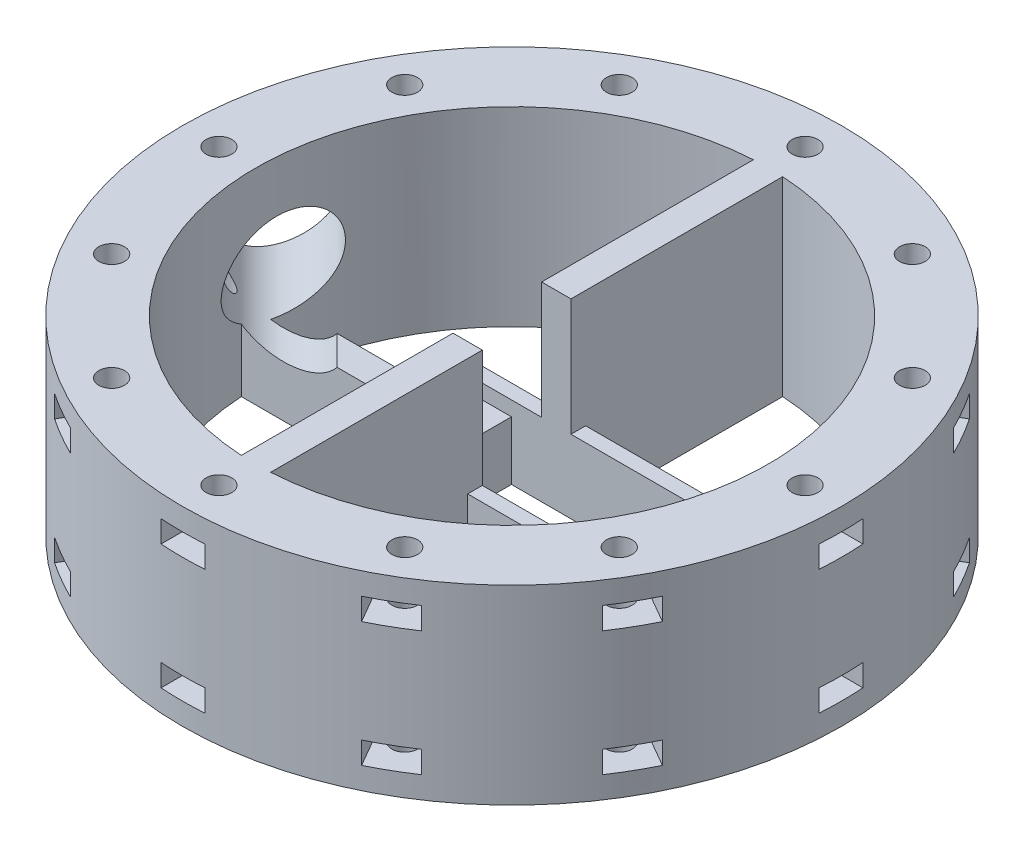
SolidWorks part; units mm, degrees
ref_plane "Front Plane" through (0, 0, 0) normal (0, 0, 1) x (1, 0, 0)
ref_plane "Top Plane" through (0, 0, 0) normal (0, 1, 0) x (1, 0, 0)
ref_plane "Right Plane" through (0, 0, 0) normal (1, 0, 0) x (0, 0, -1)
sketch "Sketch2" plane through (0, 0, 0) normal (0, 1, 0) x (1, 0, 0)
  line L0 (0, 0) -> (0, 45) construction
  circle A0 centre (0, 0) radius 45
  dimension "D1" = 90
extrude "Boss-Extrude1" add sketch "Sketch2" along normal blind 10
sketch "Sketch3" plane through (0, 10, 0) normal (0, 1, 0) x (1, 0, 0)
  line L0 (0, 45) -> (0, 0) construction
  line L1 (0, 0) -> (45, 0) construction
  line L2 (-10.95, 6.05) -> (21.3, 6.05)
  line L3 (21.3, 6.05) -> (21.3, -6.05)
  line L4 (-10.95, 6.05) -> (-10.95, -6.05)
  line L5 (-10.95, -6.05) -> (21.3, -6.05)
  circle A0 centre (0, 0) radius 45 construction
  point P12 (21.3, 0)
  point P13 (-10.95, 0)
  dimension "D1" = 32.25
  dimension "D2" = 10.95
  dimension "D3" = 12.1
extrude "Cut-Extrude1" cut sketch "Sketch3" against normal blind 2
sketch "Sketch4" plane through (0, 8, 0) normal (0, 1, 0) x (1, 0, 0)
  line L0 (5.175, 6.05) -> (5.175, -6.05) construction
  line L1 (21.3, 6.05) -> (-10.95, 6.05) construction
  line L2 (-10.95, -6.05) -> (21.3, -6.05) construction
  line L4 (-6.125, 6.05) -> (16.475, 6.05)
  line L5 (-6.125, 6.05) -> (-6.125, -6.05)
  line L6 (-6.125, -6.05) -> (16.475, -6.05)
  line L7 (16.475, 6.05) -> (16.475, -6.05)
  line L8 (-6.125, 6.05) -> (16.475, -6.05) construction
  line L9 (-6.125, -6.05) -> (16.475, 6.05) construction
  point P6 (5.175, 0)
  dimension "D1" = 22.6
extrude "Cut-Extrude2" cut sketch "Sketch4" against normal through all
sketch "Sketch6" plane through (0, 8, 0) normal (0, 1, 0) x (1, 0, 0)
  line L0 (-10.95, 0) -> (21.3, 0) construction
  line L1 (-10.95, 6.05) -> (-10.95, -6.05) construction
  line L2 (21.3, -6.05) -> (21.3, 6.05) construction
  line L3 (5.175, 6.05) -> (5.175, -6.05) construction
  line L4 (21.3, 6.05) -> (-10.95, 6.05) construction
  line L5 (-10.95, -6.05) -> (21.3, -6.05) construction
  circle A0 centre (-8.675, 0) radius 1
  circle A1 centre (19.025, 0) radius 1
  dimension "D1" = 2
  dimension "D2" = 27.7
extrude "Cut-Extrude4" cut sketch "Sketch6" against normal through all
sketch "Sketch9" plane through (0, 10, 0) normal (0, 1, 0) x (1, 0, 0)
  line L0 (-10.95, 6.05) -> (-10.95, -6.05) construction
  line L1 (-12.95, 8.05) -> (-2, 8.05)
  line L2 (-12.95, 8.05) -> (-12.95, 2)
  line L3 (-12.95, -8.05) -> (-2, -8.05)
  line L4 (-12.95, 2) -> (-34.9428, 2)
  line L6 (21.3, 6.05) -> (-10.95, 6.05) construction
  line L7 (0, 0) -> (-31.825, 0) construction
  line L8 (0, 0) -> (0, 31.7606) construction
  line L9 (-2, 34.9428) -> (-2, 8.05)
  line L10 (2, 34.9428) -> (2, 8.05)
  line L11 (-12.95, -2) -> (-34.9428, -2)
  line L12 (2, -34.9428) -> (2, -8.05)
  line L13 (-2, -34.9428) -> (-2, -8.05)
  line L14 (-12.95, -2) -> (-12.95, -8.05)
  line L15 (2, 8.05) -> (34.0617, 8.05)
  line L16 (2, -8.05) -> (34.0617, -8.05)
  arc A0 (34.0617, 8.05) -> (2, 34.9428) centre (0, 0) ccw
  arc A1 (-34.9428, -2) -> (-2, -34.9428) centre (0, 0) ccw
  arc A2 (-2, 34.9428) -> (-34.9428, 2) centre (0, 0) ccw
  arc A3 (2, -34.9428) -> (34.0617, -8.05) centre (0, 0) ccw
  dimension "D1" = 70
  dimension "D2" = 2
  dimension "D4" = 2
  dimension "D5" = 4
  dimension "D6" = 4
extrude "Cut-Extrude5" cut sketch "Sketch9" against normal through all
sketch "Sketch10" plane through (0, 0, 0) normal (0, -1, 0) x (1, 0, 0)
  circle A0 centre (0, 0) radius 40 construction
  circle A1 centre (-40, 0) radius 1.75
  circle A2 centre (-34.641, 20) radius 1.75
  circle A3 centre (-20, 34.641) radius 1.75
  circle A4 centre (0, 40) radius 1.75
  circle A5 centre (20, 34.641) radius 1.75
  circle A6 centre (34.641, 20) radius 1.75
  circle A7 centre (40, 0) radius 1.75
  circle A8 centre (34.641, -20) radius 1.75
  circle A9 centre (20, -34.641) radius 1.75
  circle A10 centre (0, -40) radius 1.75
  circle A11 centre (-20, -34.641) radius 1.75
  circle A12 centre (-34.641, -20) radius 1.75
  point P29 (0, 0)
  dimension "D1" = 80
  dimension "D2" = 3.5
  dimension "D3" = 12
sketch "Sketch13" plane through (0, 10, 0) normal (0, 1, 0) x (1, 0, 0)
  line L0 (2, -34.9428) -> (2, -8.05)
  line L1 (2, 6.05) -> (2, 34.9428)
  line L2 (-2, -8.05) -> (-2, -34.9428)
  line L3 (2, 6.05) -> (-2, 6.05)
  line L5 (2, -6.05) -> (-2, -6.05)
  line L6 (-2, 34.9428) -> (-2, 6.05)
  line L8 (2, -8.05) -> (2, -6.05)
  line L9 (-2, -6.05) -> (-2, -8.05)
  circle A0 centre (0, 0) radius 45
  arc A1 (34.9857, 1) -> (2, 34.9428) centre (0, 0) ccw
  arc A2 (-2, 34.9428) -> (-34.9428, 2) centre (0, 0) ccw
  arc A3 (-34.9428, 2) -> (-2, -34.9428) centre (0, 0) ccw
  arc A4 (2, -34.9428) -> (34.9857, 1) centre (0, 0) ccw
  dimension "D1" = 90
extrude "Boss-Extrude2" add sketch "Sketch13" along normal blind 16
extrude "Cut-Extrude7" cut sketch "Sketch10" against normal through all
ref_plane "Plane1" through (0, 23, 0) normal (0, 1, 0) x (1, 0, 0)
sketch "Sketch14" plane through (0, 23, 0) normal (0, 1, 0) x (1, 0, 0)
  line L0 (31.641, -18.2679) -> (31.641, -21.7321)
  line L1 (36.5359, 0) -> (38.2679, -3)
  line L2 (38.2679, -3) -> (44.8999, -3)
  line L3 (34.641, -16.5359) -> (31.641, -18.2679)
  line L4 (40.3844, -19.8519) -> (34.641, -16.5359)
  line L5 (44.8999, 3) -> (38.2679, 3)
  line L6 (38.2679, 3) -> (36.5359, 0)
  line L7 (43.4641, 0) -> (42.5981, 1.5) [skipped]
  line L8 (41.7321, -3) -> (42.5981, -1.5) [skipped]
  line L9 (31.641, -21.7321) -> (37.3844, -25.048)
  line L10 (18.2679, -31.641) -> (16.5359, -34.641)
  line L11 (21.7321, -31.641) -> (18.2679, -31.641)
  line L12 (25.048, -37.3844) -> (21.7321, -31.641)
  line L13 (16.5359, -34.641) -> (19.8519, -40.3844)
  line L14 (0, -36.5359) -> (-3, -38.2679)
  line L15 (3, -38.2679) -> (0, -36.5359)
  line L16 (3, -44.8999) -> (3, -38.2679)
  line L17 (-3, -38.2679) -> (-3, -44.8999)
  line L18 (-18.2679, -31.641) -> (-21.7321, -31.641)
  line L19 (-16.5359, -34.641) -> (-18.2679, -31.641)
  line L20 (-19.8519, -40.3844) -> (-16.5359, -34.641)
  line L21 (-21.7321, -31.641) -> (-25.048, -37.3844)
  line L22 (-31.641, -18.2679) -> (-34.641, -16.5359)
  line L23 (-31.641, -21.7321) -> (-31.641, -18.2679)
  line L24 (-37.3844, -25.048) -> (-31.641, -21.7321)
  line L25 (-34.641, -16.5359) -> (-40.3844, -19.8519)
  line L26 (-36.5359, 0) -> (-38.2679, 3)
  line L27 (-38.2679, -3) -> (-36.5359, 0)
  line L28 (-44.8999, -3) -> (-38.2679, -3)
  line L29 (-38.2679, 3) -> (-44.8999, 3)
  line L30 (-31.641, 18.2679) -> (-31.641, 21.7321)
  line L31 (-34.641, 16.5359) -> (-31.641, 18.2679)
  line L32 (-40.3844, 19.8519) -> (-34.641, 16.5359)
  line L33 (-31.641, 21.7321) -> (-37.3844, 25.048)
  line L34 (-18.2679, 31.641) -> (-16.5359, 34.641)
  line L35 (-21.7321, 31.641) -> (-18.2679, 31.641)
  line L36 (-25.048, 37.3844) -> (-21.7321, 31.641)
  line L37 (-16.5359, 34.641) -> (-19.8519, 40.3844)
  line L38 (0, 36.5359) -> (3, 38.2679)
  line L39 (-3, 38.2679) -> (0, 36.5359)
  line L40 (-3, 44.8999) -> (-3, 38.2679)
  line L41 (3, 38.2679) -> (3, 44.8999)
  line L42 (18.2679, 31.641) -> (21.7321, 31.641)
  line L43 (16.5359, 34.641) -> (18.2679, 31.641)
  line L44 (19.8519, 40.3844) -> (16.5359, 34.641)
  line L45 (21.7321, 31.641) -> (25.048, 37.3844)
  line L46 (31.641, 18.2679) -> (34.641, 16.5359)
  line L47 (31.641, 21.7321) -> (31.641, 18.2679)
  line L48 (37.3844, 25.048) -> (31.641, 21.7321)
  line L49 (34.641, 16.5359) -> (40.3844, 19.8519)
  circle A0 centre (40, 0) radius 3 construction
  arc A1 (44.8999, -3) -> (44.8999, 3) centre (0, 0) ccw
  arc A2 (37.3844, -25.048) -> (40.3844, -19.8519) centre (0, 0) ccw
  arc A3 (19.8519, -40.3844) -> (25.048, -37.3844) centre (0, 0) ccw
  arc A4 (-3, -44.8999) -> (3, -44.8999) centre (0, 0) ccw
  arc A5 (-25.048, -37.3844) -> (-19.8519, -40.3844) centre (0, 0) ccw
  arc A6 (-40.3844, -19.8519) -> (-37.3844, -25.048) centre (0, 0) ccw
  arc A7 (-44.8999, 3) -> (-44.8999, -3) centre (0, 0) ccw
  arc A8 (-37.3844, 25.048) -> (-40.3844, 19.8519) centre (0, 0) ccw
  arc A9 (-19.8519, 40.3844) -> (-25.048, 37.3844) centre (0, 0) ccw
  arc A10 (3, 44.8999) -> (-3, 44.8999) centre (0, 0) ccw
  arc A11 (25.048, 37.3844) -> (19.8519, 40.3844) centre (0, 0) ccw
  arc A12 (40.3844, 19.8519) -> (37.3844, 25.048) centre (0, 0) ccw
  point P71 (0, 0)
  dimension "D1" = 6
  dimension "D2" = 12
extrude "Cut-Extrude8" cut sketch "Sketch14" against normal blind 3
ref_plane "Plane2" through (0, 13, 0) normal (0, 1, 0) x (1, 0, 0)
mirror "Mirror1" about plane through (0, 13, 0) normal (0, 1, 0) of "Cut-Extrude8"
ref_plane "Plane3" through (0, 0, 0) normal (-0.7071, 0, -0.7071) x (-0.7071, 0, 0.7071)
sketch "Sketch15" plane through (0, 0, 0) normal (-0.7071, 0, -0.7071) x (-0.7071, 0, 0.7071)
  line L1 (14.5187, 20) -> (29.6277, 20) construction
  line L2 (14.5187, 6) -> (29.6277, 6) construction
  line L3 (22.0732, 20) -> (22.0732, 6) construction
  circle A0 centre (22.0732, 13) radius 6
  dimension "D1" = 12
extrude "Cut-Extrude9" cut sketch "Sketch15" along normal through all
